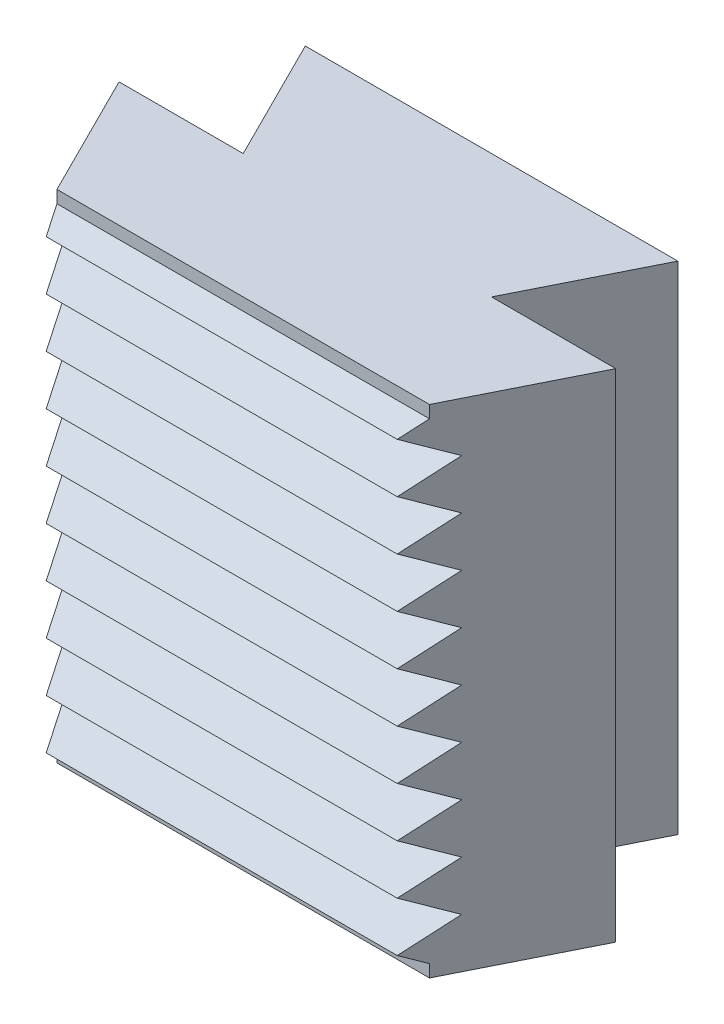
SolidWorks part; units mm, degrees
ref_plane "Front Plane" through (0, 0, 0) normal (0, 0, 1) x (1, 0, 0)
ref_plane "Top Plane" through (0, 0, 0) normal (0, 1, 0) x (1, 0, 0)
ref_plane "Right Plane" through (0, 0, 0) normal (1, 0, 0) x (0, 0, -1)
sketch "Sketch1" plane through (0, 0, 0) normal (0, 1, 0) x (1, 0, 0)
  line L0 (-3.75, 0) -> (3.75, 0)
  line L1 (3.75, 0) -> (5, 2.5)
  line L3 (-5, 2.5) -> (-3.75, 0)
  line L8 (-5, 2.5) -> (-2.5, 2.5)
  line L9 (-2.5, 2.5) -> (-3.75, 5)
  line L10 (-3.75, 5) -> (3.75, 5)
  line L11 (3.75, 5) -> (2.5, 2.5)
  line L12 (2.5, 2.5) -> (5, 2.5)
  line L13 (0, 0) -> (0, 5) construction
  point P4 (0, 0)
  dimension "D1" = 2.5
  dimension "D2" = 1.25
  dimension "D3" = 2.5
  dimension "D4" = 1.25
  dimension "D5" = 2.5
  dimension "D6" = 2.5
  dimension "D7" = 7.5
  dimension "D8" = 7.5
  dimension "D9" = 2.5
extrude "Boss-Extrude1" add sketch "Sketch1" along normal blind 5 and the other way blind 5
sketch "Sketch3" plane through (0, 0, 0) normal (1, 0, 0) x (0, 0, -1)
  line L1 (-0.433, 4.5) -> (0.2165, 4.125)
  line L4 (-0.433, 4.5) -> (0.433, 4.5) construction
  line L5 (0.2165, 4.125) -> (0.2165, 4.875)
  line L6 (0.2165, 4.875) -> (-0.433, 4.5)
  line L7 (0.2165, 3.875) -> (-0.433, 3.5)
  line L8 (0.433, 5) -> (0.433, 4) construction
  line L9 (0, 5) -> (2.5, 5) construction
  line L10 (0.433, 4) -> (-0.433, 4.5) construction
  line L11 (-0.433, 4.5) -> (0.433, 5) construction
  line L12 (0, -5) -> (0, 5) construction
  line L13 (-0.433, 3.5) -> (0.2165, 3.125)
  line L14 (0.2165, 3.125) -> (0.2165, 3.875)
  line L15 (0.2165, 2.875) -> (-0.433, 2.5)
  line L16 (-0.433, 2.5) -> (0.2165, 2.125)
  line L17 (0.2165, 2.125) -> (0.2165, 2.875)
  line L18 (0.2165, 1.875) -> (-0.433, 1.5)
  line L19 (-0.433, 1.5) -> (0.2165, 1.125)
  line L20 (0.2165, 1.125) -> (0.2165, 1.875)
  line L21 (0.2165, 0.875) -> (-0.433, 0.5)
  line L22 (-0.433, 0.5) -> (0.2165, 0.125)
  line L23 (0.2165, 0.125) -> (0.2165, 0.875)
  line L24 (0.2165, -0.125) -> (-0.433, -0.5)
  line L25 (-0.433, -0.5) -> (0.2165, -0.875)
  line L26 (0.2165, -0.875) -> (0.2165, -0.125)
  line L27 (0.2165, -1.125) -> (-0.433, -1.5)
  line L28 (-0.433, -1.5) -> (0.2165, -1.875)
  line L29 (0.2165, -1.875) -> (0.2165, -1.125)
  line L30 (0.2165, -2.125) -> (-0.433, -2.5)
  line L31 (-0.433, -2.5) -> (0.2165, -2.875)
  line L32 (0.2165, -2.875) -> (0.2165, -2.125)
  line L33 (0.2165, -3.125) -> (-0.433, -3.5)
  line L34 (-0.433, -3.5) -> (0.2165, -3.875)
  line L35 (0.2165, -3.875) -> (0.2165, -3.125)
  line L36 (0.2165, -4.125) -> (-0.433, -4.5)
  line L37 (-0.433, -4.5) -> (0.2165, -4.875)
  line L38 (0.2165, -4.875) -> (0.2165, -4.125)
  line L39 (0.2165, 4.875) -> (0.2165, 3.875) construction
  point P3 (0, 4.5)
  dimension "D1" = 1
  dimension "D2" = 1
  dimension "D3" = 1
  dimension "D4" = 0.75
  dimension "D5" = 1
extrude "Boss-Extrude2" add sketch "Sketch3" along normal up to surface and the other way up to surface up to face at (4.375, 0, -1.25) other way up to face at (-4.375, 0, -1.25)
sketch "Sketch4" plane through (0, 0, 0) normal (1, 0, 0) x (0, 0, -1)
  line L0 (-0.433, 4.5) -> (0.433, 4) construction
  line L1 (-0.433, 4.5) -> (-0.433, 3.5) construction
  line L2 (-0.433, 3.5) -> (0.433, 4) construction
  line L3 (0.433, 4) -> (-0.2165, 4.375)
  line L6 (-0.2165, 4.375) -> (-0.2165, 3.625)
  line L7 (0, 3.75) -> (-0.433, 3.5) construction
  line L8 (-0.2165, 3.625) -> (0.433, 4)
  line L9 (-0.433, 4.5) -> (0, 4.25) construction
  line L10 (-0.2165, 2.625) -> (0.433, 3)
  line L11 (0.433, 3) -> (-0.2165, 3.375)
  line L12 (-0.2165, 3.375) -> (-0.2165, 2.625)
  line L13 (-0.2165, 1.625) -> (0.433, 2)
  line L14 (0.433, 2) -> (-0.2165, 2.375)
  line L15 (-0.2165, 2.375) -> (-0.2165, 1.625)
  line L16 (-0.2165, 0.625) -> (0.433, 1)
  line L17 (0.433, 1) -> (-0.2165, 1.375)
  line L18 (-0.2165, 1.375) -> (-0.2165, 0.625)
  line L19 (-0.2165, -0.375) -> (0.433, 0)
  line L20 (0.433, 0) -> (-0.2165, 0.375)
  line L21 (-0.2165, 0.375) -> (-0.2165, -0.375)
  line L22 (-0.2165, -1.375) -> (0.433, -1)
  line L23 (0.433, -1) -> (-0.2165, -0.625)
  line L24 (-0.2165, -0.625) -> (-0.2165, -1.375)
  line L25 (-0.2165, -2.375) -> (0.433, -2)
  line L26 (0.433, -2) -> (-0.2165, -1.625)
  line L27 (-0.2165, -1.625) -> (-0.2165, -2.375)
  line L28 (-0.2165, -3.375) -> (0.433, -3)
  line L29 (0.433, -3) -> (-0.2165, -2.625)
  line L30 (-0.2165, -2.625) -> (-0.2165, -3.375)
  line L31 (-0.2165, -4.375) -> (0.433, -4)
  line L32 (0.433, -4) -> (-0.2165, -3.625)
  line L33 (-0.2165, -3.625) -> (-0.2165, -4.375)
  line L34 (-0.2165, 3.625) -> (-0.2165, 2.625) construction
  dimension "D1" = 1
  dimension "D2" = 1
  dimension "D3" = 1
extrude "Cut-Extrude1" cut sketch "Sketch4" against normal through all both and the other way through all
